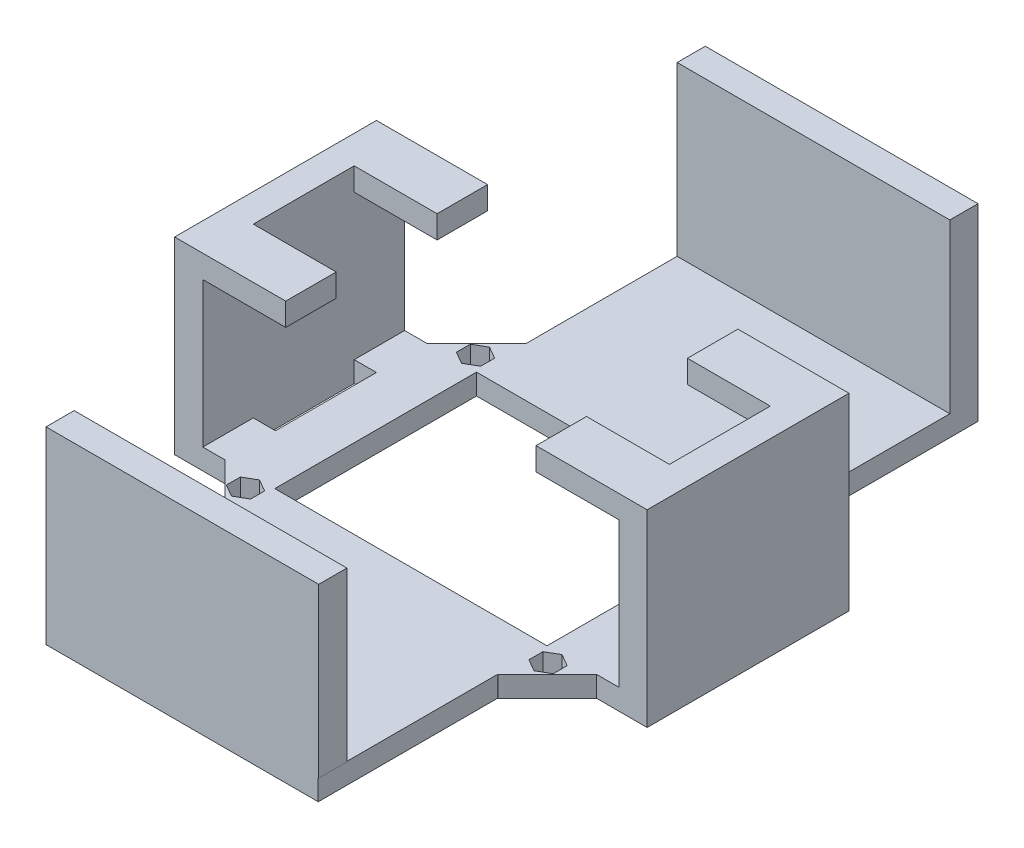
SolidWorks part; units mm, degrees
ref_plane "Front Plane" through (0, 0, 0) normal (0, 0, 1) x (1, 0, 0)
ref_plane "Top Plane" through (0, 0, 0) normal (0, 1, 0) x (1, 0, 0)
ref_plane "Right Plane" through (0, 0, 0) normal (1, 0, 0) x (0, 0, -1)
sketch "Sketch2" plane through (0, 0, 0) normal (0, 1, 0) x (1, 0, 0)
  line L0 (-32.8436, 36.3397) -> (-32.8436, 24.3397)
  line L1 (-32.8436, 24.3397) -> (-44.8436, 24.3397)
  line L2 (-44.8436, 24.3397) -> (-32.8436, 36.3397)
  line L3 (0, 57.5251) -> (0, -40.7887) construction
  line L4 (-92.2724, 0) -> (92.8059, 0) construction
  line L27 (32.8436, 24.3397) -> (44.8436, 24.3397)
  line L28 (32.8436, 36.3397) -> (32.8436, 24.3397)
  line L29 (44.8436, 24.3397) -> (32.8436, 36.3397)
  line L30 (44.8436, -24.3397) -> (32.8436, -36.3397)
  line L31 (32.8436, -36.3397) -> (32.8436, -24.3397)
  line L32 (32.8436, -24.3397) -> (44.8436, -24.3397)
  line L45 (-44.8436, -24.3397) -> (-32.8436, -36.3397)
  line L46 (-32.8436, -24.3397) -> (-44.8436, -24.3397)
  line L47 (-32.8436, -36.3397) -> (-32.8436, -24.3397)
  line L48 (39.425, -26.0613) -> (39.425, -29.4387)
  line L49 (-36.5, -31.1275) -> (-33.575, -29.4387)
  line L50 (-33.575, -29.4387) -> (-33.575, -26.0613)
  line L51 (-33.575, -26.0613) -> (-36.5, -24.3725)
  line L52 (-36.5, -24.3725) -> (-39.425, -26.0613)
  line L53 (-39.425, -26.0613) -> (-39.425, -29.4387)
  line L54 (-39.425, -29.4387) -> (-36.5, -31.1275)
  line L55 (39.425, -29.4387) -> (36.5, -31.1275)
  line L56 (36.5, -31.1275) -> (33.575, -29.4387)
  line L57 (33.575, -29.4387) -> (33.575, -26.0613)
  line L58 (33.575, -26.0613) -> (36.5, -24.3725)
  line L59 (36.5, -24.3725) -> (39.425, -26.0613)
  line L60 (33.575, 29.4387) -> (33.575, 26.0613)
  line L61 (36.5, 31.1275) -> (33.575, 29.4387)
  line L62 (39.425, 29.4387) -> (36.5, 31.1275)
  line L63 (39.425, 26.0613) -> (39.425, 29.4387)
  line L64 (36.5, 24.3725) -> (39.425, 26.0613)
  line L65 (33.575, 26.0613) -> (36.5, 24.3725)
  line L66 (-33.575, 29.4387) -> (-33.575, 26.0613)
  line L67 (-36.5, 31.1275) -> (-33.575, 29.4387)
  line L68 (-39.425, 29.4387) -> (-36.5, 31.1275)
  line L69 (-39.425, 26.0613) -> (-39.425, 29.4387)
  line L70 (-33.575, 26.0613) -> (-36.5, 24.3725)
  line L71 (-36.5, 24.3725) -> (-39.425, 26.0613)
  circle A7 centre (-36.5, -27.75) radius 2.925 construction
  point P0 (-36.5, 27.75)
  point P1 (-36.5, -27.75)
  point P2 (36.5, -27.75)
  point P3 (36.5, 27.75)
  point P43 (36.5, -27.75)
  point P45 (0, 0)
  point P55 (-36.5, -27.75)
  dimension "D6" = 12
  dimension "D2" = 73
  dimension "D3" = 55.5
  dimension "D8" = 73
  dimension "D9" = 55.5
  dimension "D10" = 27.75
  dimension "D11" = 5
  dimension "D12" = 36.5
  dimension "D13" = 36.5
  dimension "D5" = 12
  dimension "D14" = 27.75
  dimension "D15" = 27.75
  dimension "D16" = 5.85
extrude "Boss-Extrude1" add sketch "Sketch2" along normal blind 20
sketch "Sketch6" plane through (-32.8436, 0, 0) normal (1, 0, 0) x (0, 0, -1)
  line L0 (36.3397, 20) -> (36.3397, 0) construction
  line L1 (24.3397, 20) -> (36.3397, 20)
  line L2 (24.3397, 20) -> (24.3397, 15)
  line L3 (24.3397, 15) -> (36.3397, 15)
  line L4 (36.3397, 20) -> (36.3397, 15)
  line L5 (-24.3397, 20) -> (-24.3397, 0) construction
  line L6 (-36.3397, 20) -> (-24.3397, 20)
  line L7 (-36.3397, 20) -> (-36.3397, 15)
  line L8 (-36.3397, 15) -> (-24.3397, 15)
  line L9 (-24.3397, 20) -> (-24.3397, 15)
  dimension "D1" = 5
  dimension "D2" = 5
extrude "Boss-Extrude5" add sketch "Sketch6" along normal blind 65.8
sketch "Sketch7" plane through (0, 0, 24.3397) normal (0, 0, -1) x (-1, 0, 0)
  line L1 (-44.8436, 20) -> (-32.8436, 20)
  line L2 (-44.8436, 20) -> (-44.8436, 15)
  line L3 (-44.8436, 15) -> (-32.8436, 15)
  line L4 (-32.8436, 20) -> (-32.8436, 15)
  line L5 (32.8436, 15) -> (44.8436, 15)
  line L6 (32.8436, 15) -> (32.8436, 20)
  line L7 (32.8436, 20) -> (44.8436, 20)
  line L8 (44.8436, 15) -> (44.8436, 20)
extrude "Boss-Extrude6" add sketch "Sketch7" along normal blind 48.7
sketch "Sketch8" plane through (44.8436, 0, 0) normal (1, 0, 0) x (0, 0, -1)
  line L0 (24.3397, 15) -> (-24.3397, 15) construction
  line L1 (-24.3397, 20) -> (-12.1647, 20)
  line L2 (-24.3397, 20) -> (-24.3397, 15)
  line L3 (-24.3397, 15) -> (-12.1647, 15)
  line L4 (-12.1647, 20) -> (-12.1647, 15)
  line L5 (24.3603, 20) -> (-24.3397, 20) construction
  line L6 (24.3603, 15) -> (12.1853, 15)
  line L7 (24.3603, 15) -> (24.3603, 20)
  line L8 (24.3603, 20) -> (12.1853, 20)
  line L9 (12.1853, 15) -> (12.1853, 20)
  dimension "D1" = 12.175
  dimension "D2" = 12.175
extrude "Boss-Extrude7" add sketch "Sketch8" along normal blind 12.16
sketch "Sketch9" plane through (-44.8436, 0, 0) normal (-1, 0, 0) x (0, 0, 1)
  line L0 (-24.3397, 15) -> (24.3397, 15) construction
  line L1 (-24.3603, 20) -> (-12.1853, 20)
  line L2 (-24.3603, 20) -> (-24.3603, 15)
  line L3 (-24.3603, 15) -> (-12.1853, 15)
  line L4 (-12.1853, 20) -> (-12.1853, 15)
  line L5 (-24.3603, 20) -> (24.3397, 20) construction
  line L6 (24.3397, 15) -> (12.1647, 15)
  line L7 (24.3397, 15) -> (24.3397, 20)
  line L8 (24.3397, 20) -> (12.1647, 20)
  line L9 (12.1647, 15) -> (12.1647, 20)
  dimension "D1" = 12.175
  dimension "D2" = 12.175
extrude "Boss-Extrude8" add sketch "Sketch9" along normal blind 12.16
sketch "Sketch11" plane through (0, 20, 0) normal (0, 1, 0) x (1, 0, 0)
  line L0 (-57.0036, -24.3397) -> (-44.8436, -24.3397) construction
  line L1 (-50.2036, -24.3397) -> (-57.0036, -24.3397)
  line L2 (-50.2036, -24.3397) -> (-50.2036, -12.1647)
  line L3 (-50.2036, -12.1647) -> (-57.0036, -12.1647)
  line L4 (-57.0036, -24.3397) -> (-57.0036, -12.1647)
  line L5 (-57.0036, 12.1853) -> (-44.8436, 12.1853) construction
  line L6 (-57.0036, 24.3603) -> (-50.2036, 24.3603)
  line L7 (-57.0036, 24.3603) -> (-57.0036, 12.1853)
  line L8 (-57.0036, 12.1853) -> (-50.2036, 12.1853)
  line L9 (-50.2036, 24.3603) -> (-50.2036, 12.1853)
  line L10 (57.0036, 12.1853) -> (44.8436, 12.1853) construction
  line L11 (57.0036, 24.3603) -> (50.2036, 24.3603)
  line L12 (57.0036, 24.3603) -> (57.0036, 12.1853)
  line L13 (57.0036, 12.1853) -> (50.2036, 12.1853)
  line L14 (50.2036, 24.3603) -> (50.2036, 12.1853)
  line L15 (57.0036, -24.3397) -> (44.8436, -24.3397) construction
  line L16 (57.0036, -12.1647) -> (50.2036, -12.1647)
  line L17 (57.0036, -12.1647) -> (57.0036, -24.3397)
  line L18 (57.0036, -24.3397) -> (50.2036, -24.3397)
  line L19 (50.2036, -12.1647) -> (50.2036, -24.3397)
  dimension "D1" = 6.8
  dimension "D2" = 5.36
  dimension "D3" = 6.8
  dimension "D4" = 6.8
  dimension "D5" = 6.8
extrude "Boss-Extrude9" add sketch "Sketch11" along normal blind 40.5
sketch "Sketch12" plane through (-50.2036, 0, 0) normal (1, 0, 0) x (0, 0, -1)
  line L0 (-12.1647, 60.5) -> (-12.1647, 20) construction
  line L1 (-24.3397, 60.5) -> (-12.1647, 60.5)
  line L2 (-24.3397, 60.5) -> (-24.3397, 55)
  line L3 (-24.3397, 55) -> (-12.1647, 55)
  line L4 (-12.1647, 60.5) -> (-12.1647, 55)
  line L5 (24.3603, 60.5) -> (24.3603, 20) construction
  line L6 (12.1853, 60.5) -> (24.3603, 60.5)
  line L7 (12.1853, 60.5) -> (12.1853, 55)
  line L8 (12.1853, 55) -> (24.3603, 55)
  line L9 (24.3603, 60.5) -> (24.3603, 55)
  dimension "D1" = 5.5
  dimension "D2" = 5.5
extrude "Boss-Extrude10" add sketch "Sketch12" along normal blind 20
sketch "Sketch13" plane through (50.2036, 0, 0) normal (-1, 0, 0) x (0, 0, 1)
  line L0 (-12.1853, 60.5) -> (-12.1853, 20) construction
  line L1 (-24.3603, 60.5) -> (-12.1853, 60.5)
  line L2 (-24.3603, 60.5) -> (-24.3603, 55)
  line L3 (-24.3603, 55) -> (-12.1853, 55)
  line L4 (-12.1853, 60.5) -> (-12.1853, 55)
  line L5 (24.3397, 60.5) -> (24.3397, 20) construction
  line L6 (12.1647, 60.5) -> (24.3397, 60.5)
  line L7 (12.1647, 60.5) -> (12.1647, 55)
  line L8 (12.1647, 55) -> (24.3397, 55)
  line L9 (24.3397, 60.5) -> (24.3397, 55)
  dimension "D1" = 5.5
  dimension "D2" = 5.5
extrude "Boss-Extrude11" add sketch "Sketch13" along normal blind 20
sketch "Sketch14" plane through (0, 0, 36.3397) normal (0, 0, 1) x (1, 0, 0)
  line L0 (32.8436, 15) -> (-32.8436, 15) construction
  line L1 (-32.8436, 20) -> (-20.6686, 20)
  line L2 (-32.8436, 20) -> (-32.8436, 15)
  line L3 (-32.8436, 15) -> (-20.6686, 15)
  line L4 (-20.6686, 20) -> (-20.6686, 15)
  line L5 (32.9564, 20) -> (-32.8436, 20) construction
  line L6 (32.8436, 15) -> (20.6686, 15)
  line L7 (32.8436, 15) -> (32.8436, 20)
  line L8 (32.8436, 20) -> (20.6686, 20)
  line L9 (20.6686, 15) -> (20.6686, 20)
  dimension "D1" = 12.175
  dimension "D2" = 12.175
extrude "Boss-Extrude12" add sketch "Sketch14" along normal blind 43.2
sketch "Sketch15" plane through (0, 0, -36.3397) normal (0, 0, -1) x (-1, 0, 0)
  line L0 (-32.8436, 15) -> (32.8436, 15) construction
  line L1 (-32.9564, 20) -> (-20.7814, 20)
  line L2 (-32.9564, 20) -> (-32.9564, 15)
  line L3 (-32.9564, 15) -> (-20.7814, 15)
  line L4 (-20.7814, 20) -> (-20.7814, 15)
  line L6 (32.8436, 15) -> (20.6686, 15)
  line L7 (32.8436, 15) -> (32.8436, 20)
  line L8 (32.8436, 20) -> (20.6686, 20)
  line L9 (20.6686, 15) -> (20.6686, 20)
  dimension "D1" = 12.175
  dimension "D2" = 12.175
extrude "Boss-Extrude13" add sketch "Sketch15" along normal blind 43.2
sketch "Sketch16" plane through (0, 20, 0) normal (0, 1, 0) x (1, 0, 0)
  line L0 (-20.6686, 79.5397) -> (-20.6686, 36.3397) construction
  line L1 (-32.8436, 79.5397) -> (-20.6686, 79.5397)
  line L2 (-32.8436, 79.5397) -> (-32.8436, 72.7397)
  line L3 (-32.8436, 72.7397) -> (-20.6686, 72.7397)
  line L4 (-20.6686, 79.5397) -> (-20.6686, 72.7397)
  line L5 (32.9564, 79.5397) -> (32.9564, 36.2268) construction
  line L6 (20.7814, 79.5397) -> (32.9564, 79.5397)
  line L7 (20.7814, 79.5397) -> (20.7814, 72.7397)
  line L8 (20.7814, 72.7397) -> (32.9564, 72.7397)
  line L9 (32.9564, 79.5397) -> (32.9564, 72.7397)
  line L10 (-101.2794, 0) -> (102.0481, 0) construction
  line L11 (32.9564, -79.5397) -> (32.9564, -72.7397)
  line L12 (20.7814, -72.7397) -> (32.9564, -72.7397)
  line L13 (20.7814, -79.5397) -> (20.7814, -72.7397)
  line L14 (20.7814, -79.5397) -> (32.9564, -79.5397)
  line L15 (-20.6686, -79.5397) -> (-20.6686, -72.7397)
  line L16 (-32.8436, -72.7397) -> (-20.6686, -72.7397)
  line L17 (-32.8436, -79.5397) -> (-32.8436, -72.7397)
  line L18 (-32.8436, -79.5397) -> (-20.6686, -79.5397)
  dimension "D1" = 6.8
  dimension "D2" = 6.8
extrude "Boss-Extrude14" add sketch "Sketch16" along normal blind 40.5
sketch "Sketch17" plane through (34.5916, 0, -34.5916) normal (0.7071, 0, -0.7071) x (-0.7071, 0, -0.7071)
  line L1 (-14.4984, 15) -> (2.4721, 15)
  line L2 (-14.4984, 15) -> (-14.4984, 0)
  line L3 (-14.4984, 0) -> (2.4721, 0)
  line L4 (2.4721, 15) -> (2.4721, 0)
extrude "Cut-Extrude1" cut sketch "Sketch17" against normal blind 10
sketch "Sketch18" plane through (-34.5916, 0, -34.5916) normal (-0.7071, 0, -0.7071) x (-0.7071, 0, 0.7071)
  line L1 (-2.4721, 15) -> (14.4984, 15)
  line L2 (-2.4721, 15) -> (-2.4721, 0)
  line L3 (-2.4721, 0) -> (14.4984, 0)
  line L4 (14.4984, 15) -> (14.4984, 0)
extrude "Cut-Extrude2" cut sketch "Sketch18" against normal blind 10
sketch "Sketch19" plane through (-34.5916, 0, 34.5916) normal (-0.7071, 0, 0.7071) x (0.7071, 0, 0.7071)
  line L1 (-14.4984, 15) -> (2.4721, 15)
  line L2 (-14.4984, 15) -> (-14.4984, 0)
  line L3 (-14.4984, 0) -> (2.4721, 0)
  line L4 (2.4721, 15) -> (2.4721, 0)
extrude "Cut-Extrude3" cut sketch "Sketch19" against normal blind 10
sketch "Sketch20" plane through (34.5916, 0, 34.5916) normal (0.7071, 0, 0.7071) x (0.7071, 0, -0.7071)
  line L1 (-2.4721, 15) -> (14.4984, 15)
  line L2 (-2.4721, 15) -> (-2.4721, 0)
  line L3 (-2.4721, 0) -> (14.4984, 0)
  line L4 (14.4984, 15) -> (14.4984, 0)
extrude "Cut-Extrude4" cut sketch "Sketch20" against normal blind 10
sketch "Sketch21" plane through (-20.6686, 0, 0) normal (1, 0, 0) x (0, 0, -1)
  line L0 (-79.5397, 60.5) -> (-72.7397, 60.5)
  line L1 (-72.7397, 60.5) -> (-72.7397, 20)
  line L2 (-72.7397, 20) -> (-36.3397, 20)
  line L3 (-36.3397, 20) -> (-36.3397, 15)
  line L4 (-36.3397, 15) -> (-79.5397, 15)
  line L5 (-79.5397, 15) -> (-79.5397, 60.5)
  line L6 (79.5397, 60.5) -> (72.7397, 60.5)
  line L7 (72.7397, 60.5) -> (72.7397, 20)
  line L8 (72.7397, 20) -> (36.3397, 20)
  line L9 (36.3397, 20) -> (36.3397, 15)
  line L10 (36.3397, 15) -> (79.5397, 15)
  line L11 (79.5397, 15) -> (79.5397, 60.5)
extrude "Boss-Extrude15" add sketch "Sketch21" along normal blind 50
sketch "Sketch22" plane through (0, 0, 12.1647) normal (0, 0, -1) x (-1, 0, 0)
  line L2 (-50.2036, 55) -> (-50.2036, 20)
  line L4 (-57.0036, 15) -> (-57.0036, 60.5) construction
  line L5 (-57.0036, 20) -> (-57.0036, 60.5)
  line L8 (57.0036, 60.5) -> (57.0036, 20)
  line L9 (57.0036, 60.5) -> (57.0036, 15) construction
  line L12 (30.2036, 55) -> (50.2036, 55) construction
  line L14 (50.2036, 55) -> (50.2036, 20) construction
  line L16 (57.0036, 15) -> (44.8436, 15) construction
  line L17 (50.2036, 15) -> (57.0036, 15)
  line L18 (57.0036, 15) -> (57.0036, 20)
  line L19 (-57.0036, 20) -> (-57.0036, 15)
  line L20 (-57.0036, 15) -> (-50.2036, 15)
  line L21 (-57.0036, 15) -> (-44.8436, 15) construction
  line L26 (50.2036, 55) -> (50.2036, 20)
  line L27 (50.2036, 55) -> (50.2036, 60.5)
  line L28 (30.2036, 60.5) -> (57.0036, 60.5) construction
  line L29 (50.2036, 60.5) -> (57.0036, 60.5)
  line L30 (50.2036, 15) -> (50.2036, 20)
  line L31 (-57.0036, 60.5) -> (-50.2036, 60.5)
  line L32 (-57.0036, 60.5) -> (-30.2036, 60.5) construction
  line L33 (-50.2036, 60.5) -> (-50.2036, 55)
  line L34 (-50.2036, 20) -> (-50.2036, 15)
extrude "Boss-Extrude19" add sketch "Sketch22" along normal blind 30
sketch "Sketch24" plane through (0, 20, 0) normal (0, 1, 0) x (1, 0, 0)
  line L0 (0, 83.7429) -> (0, -88.7492) construction
  circle A0 centre (-34.9978, 22.3503) radius 0.6971
  circle A1 centre (-34.9978, 13.9447) radius 0.7392
